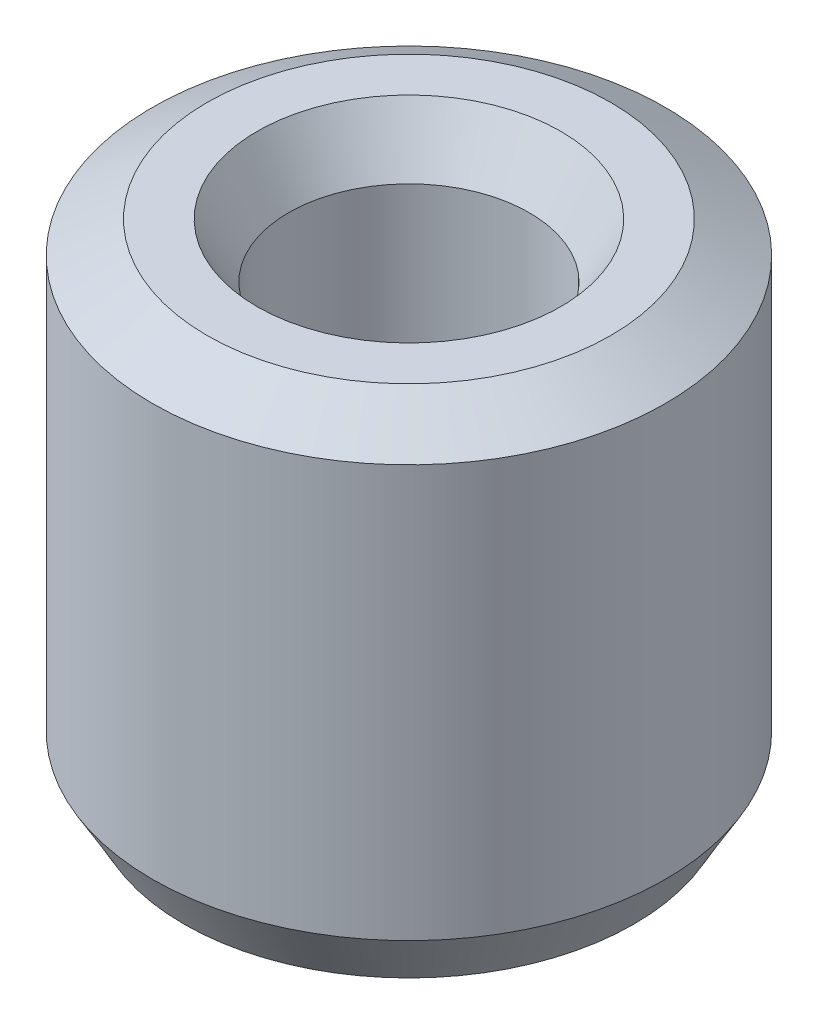
SolidWorks part; units mm, degrees
ref_plane "Front Plane" through (0, 0, 0) normal (0, 0, 1) x (1, 0, 0)
ref_plane "Top Plane" through (0, 0, 0) normal (0, 1, 0) x (1, 0, 0)
ref_plane "Right Plane" through (0, 0, 0) normal (1, 0, 0) x (0, 0, -1)
sketch "Sketch1" plane through (0, 0, 0) normal (0, 1, 0) x (1, 0, 0)
  circle A0 centre (0, 0) radius 30
  dimension "SLEEVE_OD" = 60
extrude "Boss-Extrude1" add sketch "Sketch1" along normal blind 58.2773
sketch "Sketch2" plane through (0, 0, 0) normal (0, 1, 0) x (1, 0, 0)
  circle A0 centre (0, 0) radius 14.0733
  dimension "BORE_D" = 28.1467
extrude "Cut-Extrude1" cut sketch "Sketch2" along normal through all
chamfer "Chamfer1" distance 3.6897 angle 60 4 edges at (0, 58.2773, 14.0733) (0, 0, 14.0733) (0, 0, 30) (0, 58.2773, 30) first distance on face at (0, 58.2773, 14.0733) first distance on face at (0, 0, 14.0733) first distance on face at (0, 58.2773, 30)
